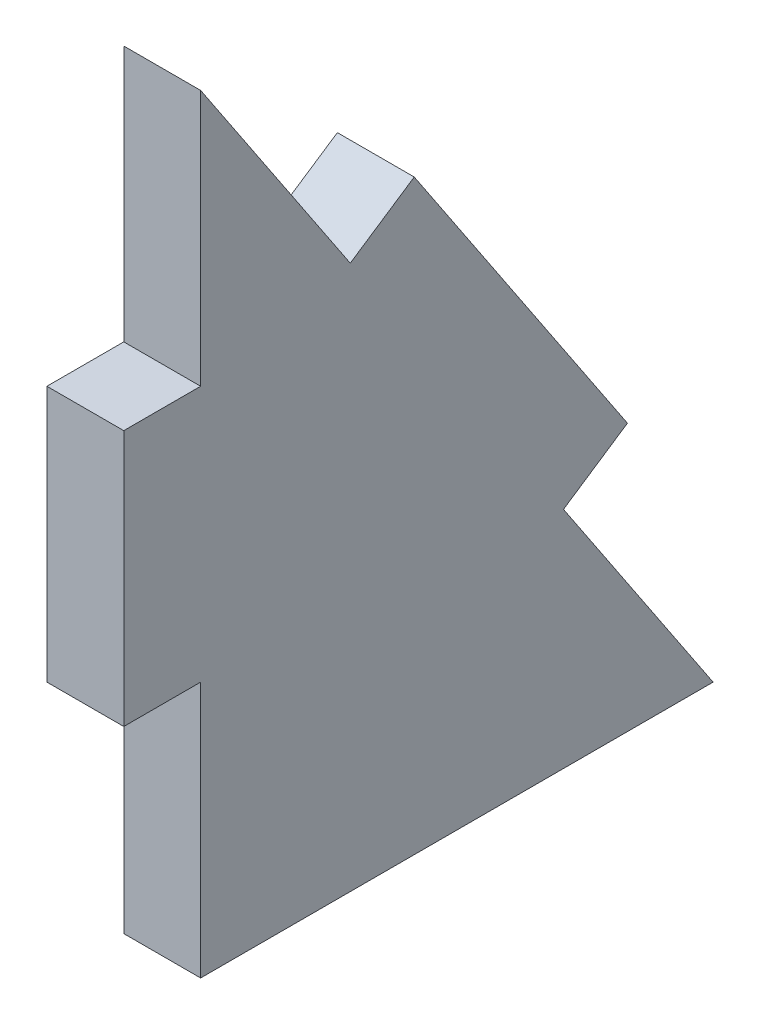
SolidWorks part; units mm, degrees
ref_plane "Front Plane" through (0, 0, 0) normal (0, 0, 1) x (1, 0, 0)
ref_plane "Top Plane" through (0, 0, 0) normal (0, 1, 0) x (1, 0, 0)
ref_plane "Right Plane" through (0, 0, 0) normal (1, 0, 0) x (0, 0, -1)
sketch "Sketch1" plane through (0, 0, 0) normal (1, 0, 0) x (0, 0, -1)
  line L0 (0, 30) -> (5.8397, 21.2404)
  line L1 (0, 0) -> (20, 0)
  line L2 (0, 0) -> (0, 10)
  line L4 (0, 20) -> (0, 30)
  line L5 (0, 20) -> (-3, 20)
  line L7 (0, 10) -> (-3, 10)
  line L8 (-3, 20) -> (-3, 10)
  line L9 (5.8397, 21.2404) -> (8.3359, 22.9045)
  line L13 (14.1603, 8.7596) -> (16.6564, 10.4237)
  line L14 (8.3359, 22.9045) -> (16.6564, 10.4237)
  line L15 (14.1603, 8.7596) -> (20, 0)
  dimension "D1" = 20
  dimension "D2" = 30
  dimension "D3" = 10
  dimension "D4" = 10
  dimension "D5" = 10.5278
  dimension "D6" = 3
  dimension "D7" = 56.31
  dimension "D9" = 15
  dimension "D10" = 3
  dimension "D12" = 90
  dimension "D13" = 90
  dimension "D14" = 90
extrude "Boss-Extrude1" add sketch "Sketch1" along normal blind 3
